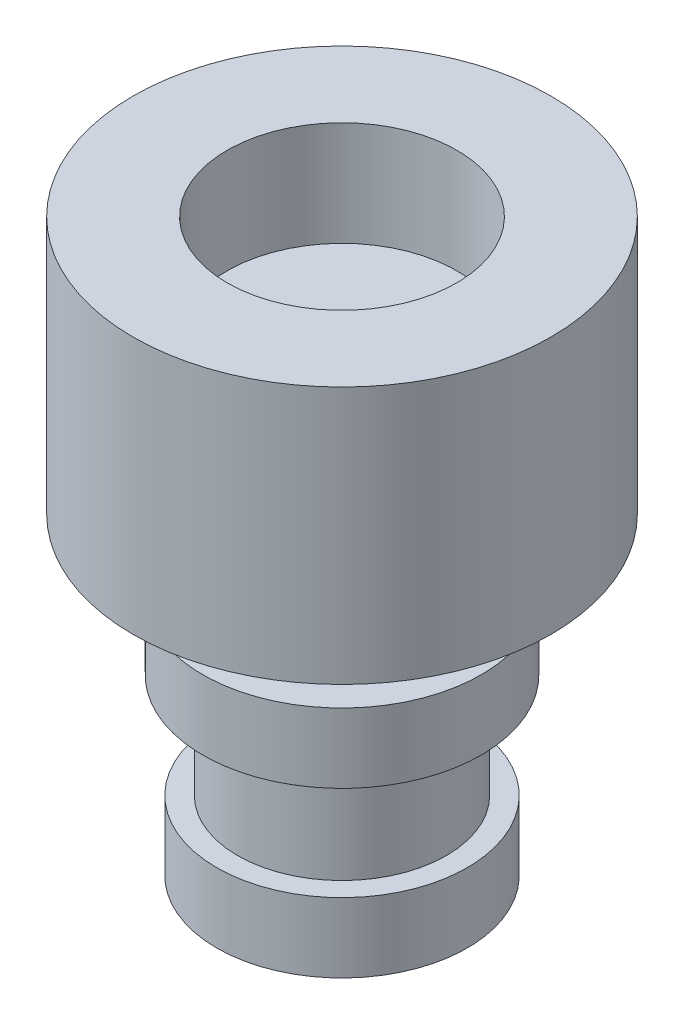
SolidWorks part; units mm, degrees
ref_plane "Front Plane" through (0, 0, 0) normal (0, 0, 1) x (1, 0, 0)
ref_plane "Top Plane" through (0, 0, 0) normal (0, 1, 0) x (1, 0, 0)
ref_plane "Right Plane" through (0, 0, 0) normal (1, 0, 0) x (0, 0, -1)
sketch "Sketch1" plane through (0, 0, 0) normal (0, 1, 0) x (1, 0, 0)
  circle A0 centre (-0.522, 0.5111) radius 1.6
  circle A1 centre (-0.522, 0.5111) radius 3
  dimension "D1" = 3.2
  dimension "D2" = 6
extrude "Boss-Extrude1" add sketch "Sketch1" along normal blind 3.7 contours A1
extrude "Boss-Extrude2" add sketch "Sketch1<3>" along normal blind 1 contours A0 region at (-0.522, 0, -0.5111)
sketch "Sketch1<3>" plane through (0, 0, 0) normal (0, 1, 0) x (1, 0, 0) same geometry as "Sketch1"
sketch "Sketch5" plane through (0, 0, 0) normal (0, -1, 0) x (1, 0, 0)
  circle A2 centre (-0.522, -0.5111) radius 1.5
  circle A3 centre (-0.522, -0.5111) radius 1.5
  dimension "D2" = 3
  dimension "D1" = 1.5
extrude "Boss-Extrude3" add sketch "Sketch5" along normal blind 1 contours A3
sketch "Sketch6" plane through (0, -1, 0) normal (0, -1, 0) x (1, 0, 0)
  circle A0 centre (-0.522, -0.5111) radius 2
  dimension "D1" = 4
extrude "Boss-Extrude4" add sketch "Sketch6" along normal blind 1
sketch "Sketch8" plane through (0, -2, 0) normal (0, -1, 0) x (-1, 0, 0)
  circle A0 centre (0.522, 0.5111) radius 1.5
  dimension "D1" = 3
extrude "Boss-Extrude5" add sketch "Sketch8" along normal blind 2.5 contours A0
sketch "Sketch10" plane through (0, -4.5, 0) normal (0, -1, 0) x (1, 0, 0)
  circle A0 centre (-0.522, -0.5111) radius 1.8
extrude "Boss-Extrude6" add sketch "Sketch10" against normal blind 1
sketch "Sketch11" plane through (0, 3.7, 0) normal (0, 1, 0) x (1, 0, 0)
  text T0 "VIII" font "Century Gothic" height in points 5
sketch "Sketch12" plane through (0, 3.7, 0) normal (0, 1, 0) x (1, 0, 0)
  circle A0 centre (-0.522, 0.5111) radius 1.65
extrude "Cut-Extrude1" cut sketch "Sketch12" against normal blind 1.5
